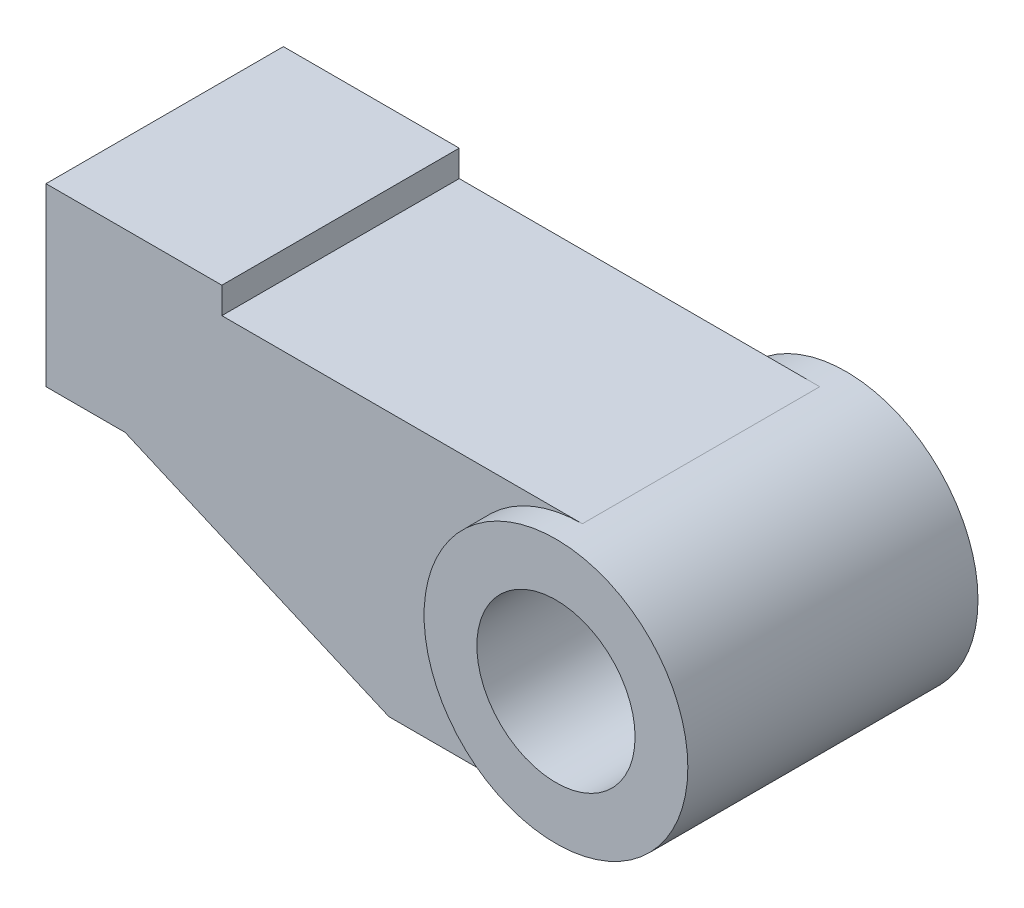
SolidWorks part; units mm, degrees
ref_plane "Front Plane" through (0, 0, 0) normal (0, 0, 1) x (1, 0, 0)
ref_plane "Top Plane" through (0, 0, 0) normal (0, 1, 0) x (1, 0, 0)
ref_plane "Right Plane" through (0, 0, 0) normal (1, 0, 0) x (0, 0, -1)
sketch "Sketch2" plane through (0, 0, 0) normal (0, 0, 1) x (1, 0, 0)
  line L0 (0, 30) -> (-82, 30)
  line L1 (-82, 30) -> (-82, 36)
  line L2 (-82, 36) -> (-122, 36)
  line L3 (-122, 36) -> (-122, -4)
  line L4 (-122, -4) -> (-104, -4)
  line L5 (-44, -30) -> (0, -30)
  line L6 (-104, -4) -> (-44, -30)
  circle A0 centre (0, 0) radius 18
  circle A1 centre (0, 0) radius 30
  dimension "D1" = 60
  dimension "D2" = 36
  dimension "D3" = 40
  dimension "D4" = 6
  dimension "D5" = 18
  dimension "D6" = 60
  dimension "D7" = 122
  dimension "D8" = 40
extrude "Boss-Extrude1" add sketch "Sketch2" along normal mid plane 54 contours A1 L0 L1 L2 L3 L4 L6 L5 | A1 A0 | A0 region at (-68.3088, 6.6382, 0) region at (20.6132, 20.6132, 0) region at (0, 0, 0)
extrude "Boss-Extrude2" add sketch "Sketch2<3>" along normal mid plane 66 contours A1
sketch "Sketch2<3>" plane through (0, 0, 0) normal (0, 0, 1) x (1, 0, 0) same geometry as "Sketch2"
extrude "Cut-Extrude1" cut sketch "Sketch2<4>" against normal blind 66 and the other way blind 66 contours A0
sketch "Sketch2<4>" plane through (0, 0, 0) normal (0, 0, 1) x (1, 0, 0) same geometry as "Sketch2"
